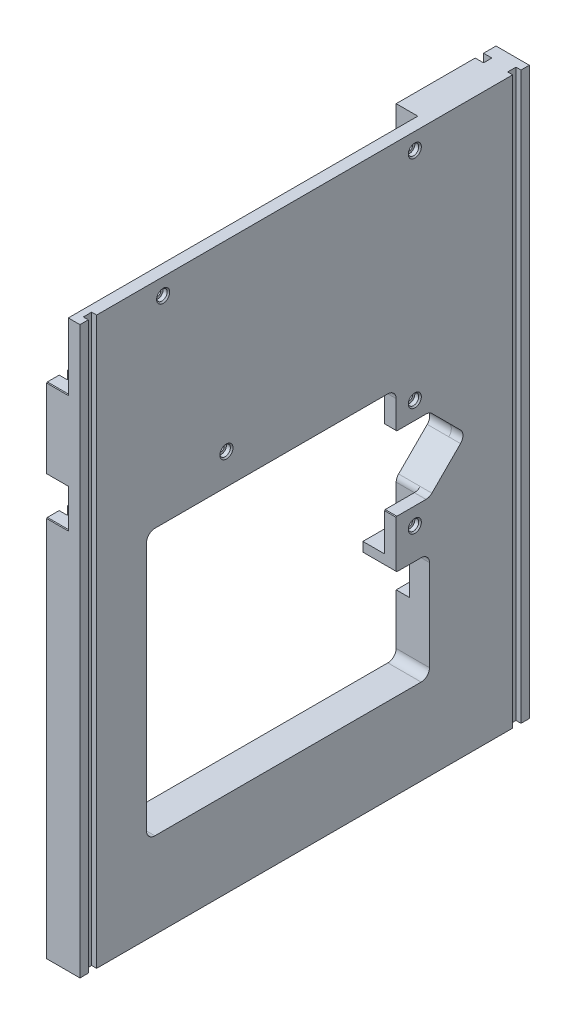
SolidWorks part; units mm, degrees
ref_plane "Front Plane" through (0, 0, 0) normal (0, 0, 1) x (1, 0, 0)
ref_plane "Top Plane" through (0, 0, 0) normal (0, 1, 0) x (1, 0, 0)
ref_plane "Right Plane" through (0, 0, 0) normal (1, 0, 0) x (0, 0, -1)
sketch "Sketch2" plane through (0, 0, 0) normal (1, 0, 0) x (0, 0, -1)
  line L1 (-215.489, 137.2751) -> (127.411, 137.2751)
  line L2 (-215.489, 137.2751) -> (-215.489, -294.5249)
  line L3 (-215.489, -294.5249) -> (127.411, -294.5249)
  line L4 (127.411, 137.2751) -> (127.411, -294.5249)
  dimension "D1" = 342.9
  dimension "D2" = 431.8
extrude "Base" add sketch "Sketch2" along normal blind 25.4
sketch "Sketch3" plane through (0, 0, 0) normal (1, 0, 0) x (0, 0, -1)
  line L0 (-44.039, -294.5249) -> (-44.039, 137.2751) construction
  line L1 (-215.489, -294.5249) -> (127.411, -294.5249) construction
  line L2 (-164.689, -25.9199) -> (-164.689, -229.1199)
  line L3 (-164.689, -229.1199) -> (51.211, -229.1199)
  line L4 (51.211, -146.9509) -> (51.211, -229.1199)
  line L5 (127.411, 137.2751) -> (-215.489, 137.2751) construction
  line L7 (-215.489, 137.2751) -> (-215.489, -294.5249) construction
  line L9 (51.211, -146.9509) -> (25.811, -146.9509)
  line L13 (-164.689, -25.9199) -> (25.811, -25.9199)
  line L14 (25.811, -146.9509) -> (25.811, -25.9199)
  dimension "D1" = 25.4
  dimension "D2" = 163.195
  dimension "D3" = 50.8
  dimension "D4" = 121.031
  dimension "D5" = 190.5
  dimension "D6" = 203.2
extrude "Cut-Extrude3" cut sketch "Sketch3" along normal up to next
sketch "Sketch4" plane through (0, 0, 0) normal (1, 0, 0) x (0, 0, -1)
  line L0 (-215.489, 137.2751) -> (-215.489, -294.5249) construction
  line L1 (19.461, -18.2999) -> (-158.339, -18.2999)
  line L2 (51.211, -15.1249) -> (51.211, 137.2751)
  line L3 (51.211, 137.2751) -> (-202.789, 137.2751)
  line L4 (-164.689, -12.5837) -> (-164.689, -3.0599)
  line L5 (51.211, -146.9509) -> (25.811, -146.9509) construction
  line L6 (25.811, -25.9199) -> (-164.689, -25.9199) construction
  line L7 (-164.689, 25.5151) -> (-215.489, 25.5151)
  line L8 (51.211, -15.1249) -> (51.211, -53.8599)
  line L9 (44.861, -139.3309) -> (25.811, -139.3309)
  line L10 (25.811, -25.9199) -> (25.811, -139.3309)
  line L11 (25.811, -25.9199) -> (-164.689, -25.9199) construction
  line L12 (25.811, -25.9199) -> (19.461, -25.9199)
  line L13 (19.461, -18.2999) -> (19.461, -25.9199)
  line L14 (51.211, -136.1559) -> (51.211, -146.9509)
  line L15 (51.211, -146.9509) -> (44.861, -146.9509)
  line L16 (44.861, -139.3309) -> (44.861, -146.9509)
  line L17 (-44.039, 137.2751) -> (-44.039, -294.5249) construction
  line L18 (-164.689, -12.5837) -> (-164.689, -25.9199)
  line L19 (-164.689, -25.9199) -> (-158.339, -25.9199)
  line L20 (-158.339, -18.2999) -> (-158.339, -25.9199)
  line L22 (-215.489, -294.5249) -> (127.411, -294.5249) construction
  line L23 (51.211, -110.2479) -> (79.405, -82.0539)
  line L24 (-164.689, -3.0599) -> (-215.489, -3.0599)
  line L25 (-215.489, 25.5151) -> (-215.489, -3.0599)
  line L26 (-164.689, 25.5151) -> (-164.689, 86.4751)
  line L27 (-202.789, 137.2751) -> (-215.489, 137.2751)
  line L28 (79.405, -82.0539) -> (51.211, -53.8599)
  line L29 (-164.689, 86.4751) -> (-215.489, 86.4751)
  line L30 (-215.489, 137.2751) -> (-215.489, 90.2851)
  line L31 (-215.489, 90.2851) -> (-215.489, 86.4751)
  line L32 (51.211, -110.2479) -> (51.211, -136.1559)
  dimension "D2" = 7.62
  dimension "D3" = 15.24
  dimension "D4" = 276.606
  dimension "D5" = 25.4
  dimension "D6" = 6.35
  dimension "D7" = 6.35
  dimension "D8" = 7.62
  dimension "D9" = 6.35
  dimension "D10" = 50.8
  dimension "D11" = 111.76
  dimension "D12" = 215.9
  dimension "D13" = 266.7
  dimension "D15" = 45
  dimension "D16" = 29.083
  dimension "D17" = 56.388
extrude "NC pocket" cut sketch "Sketch4" along normal blind 16.51
fillet "Fillet9" radius 6.35 2 edges at (8.255, -110.2479, -51.211) (8.255, -53.8599, -51.211)
fillet "Fillet6" radius 6.35 1 edges at (8.255, -82.0539, -79.405)
hole_wizard "CBORE for M4 SHCS1" positions "Sketch8" profile "Sketch10" counterbore size "M4" standard "ANSI Metric" end condition up to next
sketch "Sketch8" plane through (25.4, 0, 0) normal (1, 0, 0) x (0, 0, -1)
  line L1 (127.411, 137.2751) -> (-215.489, 137.2751) construction
  line L4 (-164.689, -3.0599) -> (-164.689, -229.1199) construction
  line L5 (51.211, -229.1199) -> (51.211, -112.8782) construction
  line L6 (-158.339, -18.2999) -> (19.461, -18.2999) construction
  point P0 (-151.989, 124.5751)
  point P5 (40.035, 124.5751)
  point P7 (40.035, -123.4559)
  point P9 (40.035, -40.5249)
  point P11 (-103.729, -2.4249)
  dimension "D2" = 12.7
  dimension "D3" = 12.7
  dimension "D4" = 11.176
  dimension "D5" = 60.96
  dimension "D6" = 15.875
  dimension "D7" = 11.176
  dimension "D8" = 165.1
  dimension "D9" = 11.176
  dimension "D10" = 82.931
  dimension "D11" = 12.7
sketch "Sketch10" plane through (25.4, 124.5751, 151.989) normal (0, 1, 0) x (0, 0, -1)
  line L0 (0, 0) -> (0, 8.89)
  line L1 (0, 8.89) -> (2.15, 8.89)
  line L3 (2.15, 8.89) -> (2.15, 4)
  line L4 (4, 4) -> (2.15, 4)
  line L5 (4, 4) -> (4, 1)
  line L6 (4, 1) -> (5, 0)
  line L7 (5, 0) -> (0, 0)
  line L8 (-4, 1) -> (-5, 0) construction
  line L11 (0, -6.35) -> (0, 107.95) construction
  dimension "Thru Hole Dia." = 4.3
  dimension "Thru Hole Depth" = 8.89
  dimension "C'Bore Dia." = 8
  dimension "C'Bore Depth" = 4
  dimension "Near C'Sink Dia." = 10
  dimension "Near C'Sink Angle" = 90
sketch "Sketch18" plane through (16.51, 0, 0) normal (-1, 0, 0) x (0, 0, 1)
  circle A0 centre (-40.035, 124.5751) radius 7.1755
  circle A1 centre (151.989, 124.5751) radius 7.1755
  circle A2 centre (103.729, -2.4249) radius 7.1755
  circle A3 centre (-40.035, -40.5249) radius 7.1755
  circle A4 centre (-40.035, -123.4559) radius 7.1755
  dimension "D1" = 14.351
  dimension "D2" = 14.351
  dimension "D3" = 14.351
  dimension "D4" = 14.351
  dimension "D5" = 14.351
extrude "Cut-Extrude4" cut sketch "Sketch18" against normal blind 1.016
hole_wizard "3/8-16 Tapped Hole1" positions "3DSketch1" profile "Sketch14" tap size "3/8-16" standard "ANSI Inch"
sketch3d "3DSketch1"
  line L0 (0, -294.5249, 215.489) -> (0, -294.5249, -127.411) construction
  line L1 (25.4, -294.5249, 215.489) -> (0, -294.5249, 215.489) construction
  point P0 (12.7, -294.5249, -70.261)
  point P2 (12.7, -294.5249, 44.039)
  point P4 (12.7, -294.5249, 158.339)
  dimension "D1" = 12.7
  dimension "D2" = 12.7
  dimension "D3" = 12.7
  dimension "D4" = 114.3
  dimension "D6" = 114.3
  dimension "D5" = 171.45
sketch "Sketch14" plane through (12.7, -294.5249, -70.261) normal (1, 0, 0) x (0, 0, -1)
  line L0 (0, 0) -> (0, 30.3247)
  line L1 (0, 30.3247) -> (3.9687, 27.94)
  line L2 (3.9687, 27.94) -> (3.9687, 0)
  line L5 (3.9687, 0) -> (0, 0)
  line L10 (0, 30.3247) -> (-3.9688, 27.94) construction
  line L11 (0, -6.35) -> (0, 107.95) construction
  dimension "Tap Drill Dia." = 7.9375
  dimension "Tap Drill Depth" = 27.94
  dimension "Drill Angle" = 118
cosmetic thread "Hole Thread1" parameters "D1"=25.4, "D2"=9.525
cosmetic thread "Hole Thread2" parameters "D1"=25.4, "D2"=9.525
cosmetic thread "Hole Thread3" parameters "D1"=25.4, "D2"=9.525
hole_wizard "3/8-16 Tapped Hole2" positions "Sketch15" profile "Sketch17" tap size "3/8-16" standard "ANSI Inch"
sketch "Sketch15" plane through (0, 0, 0) normal (-1, 0, 0) x (0, 0, 1)
  line L0 (215.489, -3.0599) -> (215.489, -294.5249) construction
  line L1 (-127.411, -294.5249) -> (-127.411, 137.2751) construction
  line L2 (215.489, -294.5249) -> (-127.411, -294.5249) construction
  point P0 (186.914, -220.8649)
  point P2 (186.914, -162.4449)
  point P4 (-98.836, -220.8649)
  point P6 (-98.836, -162.4449)
  dimension "D1" = 28.575
  dimension "D2" = 28.575
  dimension "D3" = 28.575
  dimension "D4" = 28.575
  dimension "D5" = 73.66
  dimension "D6" = 58.42
  dimension "D7" = 58.42
  dimension "D8" = 73.66
cosmetic thread "Hole Thread4" parameters "D1"=17.78, "D2"=9.525
cosmetic thread "Hole Thread5" parameters "D1"=17.78, "D2"=9.525
cosmetic thread "Hole Thread6" parameters "D1"=17.78, "D2"=9.525
cosmetic thread "Hole Thread7" parameters "D1"=17.78, "D2"=9.525
sketch "Sketch17" plane through (0, -220.8649, 186.914) normal (0, 1, 0) x (0, 0, 1)
  line L0 (0, 0) -> (0, 22.7047)
  line L1 (0, 22.7047) -> (3.9687, 20.32)
  line L2 (3.9687, 20.32) -> (3.9687, 0)
  line L5 (3.9687, 0) -> (0, 0)
  line L10 (0, 22.7047) -> (-3.9688, 20.32) construction
  line L11 (0, -6.35) -> (0, 107.95) construction
  dimension "Tap Drill Dia." = 7.9375
  dimension "Tap Drill Depth" = 20.32
  dimension "Drill Angle" = 118
sketch "Sketch20" plane through (16.51, 0, 0) normal (-1, 0, 0) x (0, 0, 1)
  line L0 (-51.211, -53.8599) -> (-25.811, -53.8599)
  line L2 (-51.211, -53.8599) -> (-79.405, -82.0539)
  line L3 (-79.405, -82.0539) -> (-51.211, -110.2479)
  line L4 (-25.811, -25.9199) -> (-25.811, -139.3309) construction
  line L6 (-25.811, -53.8599) -> (-25.811, -110.2479)
  line L7 (-25.811, -110.2479) -> (-51.211, -110.2479)
  line L8 (-51.211, -45.3946) -> (-51.211, -54.9122) construction
  line L9 (-51.211, -51.2297) -> (-51.211, 137.2751) construction
  line L10 (-51.211, -116.8371) -> (-51.211, -107.9924) construction
  line L11 (-51.211, -146.9509) -> (-51.211, -112.8782) construction
  line L12 (-74.9149, -77.5638) -> (-53.0709, -55.7198) construction
  line L13 (-53.0709, -108.388) -> (-74.9149, -86.544) construction
extrude "Cut-Extrude5" cut sketch "Sketch20" against normal up to next
fillet "Fillet1" radius 6.35 5 edges at (20.955, -25.9199, 164.689) (12.7, -229.1199, 164.689) (12.7, -229.1199, -51.211) (20.955, -146.9509, -51.211) (20.955, -25.9199, -25.811)
fillet "Fillet2" radius 6.35 3 edges at (20.955, -82.0539, -79.405) (20.955, -110.2479, -51.211) (20.955, -53.8599, -51.211)
chamfer "Chamfer1" distance 0.508 angle 45 9 edges at (8.255, -3.0599, 215.489) (8.255, -3.0599, 164.689) (8.255, 25.5151, 215.489) (8.255, 25.5151, 164.689) (8.255, 86.4751, 215.489) (8.255, 86.4751, 164.689) (12.7, -146.9509, -25.811) (20.955, -110.2479, -25.811) (20.955, -53.8599, -25.811)
sketch "Sketch21" plane through (0, 0, 0) normal (-1, 0, 0) x (0, 0, 1)
  line L0 (215.489, -294.5249) -> (-127.411, -294.5249) construction
  line L1 (205.964, -294.5249) -> (199.614, -294.5249)
  line L2 (205.964, -294.5249) -> (205.964, 137.2751)
  line L3 (205.964, 137.2751) -> (199.614, 137.2751)
  line L4 (199.614, -294.5249) -> (199.614, 137.2751)
  line L5 (-127.411, 137.2751) -> (-51.211, 137.2751) construction
  line L6 (215.489, -3.5679) -> (215.489, -294.5249) construction
  line L7 (-127.411, -294.5249) -> (-127.411, 137.2751) construction
  line L8 (-111.536, -294.5249) -> (-117.886, -294.5249)
  line L9 (-111.536, -294.5249) -> (-111.536, 137.2751)
  line L10 (-111.536, 137.2751) -> (-117.886, 137.2751)
  line L11 (-117.886, -294.5249) -> (-117.886, 137.2751)
  dimension "D1" = 6.35
  dimension "D2" = 9.525
  dimension "D3" = 6.35
  dimension "D4" = 9.525
extrude "Cut-Extrude6" cut sketch "Sketch21" against normal blind 6.35
sketch "Sketch22" plane through (25.4, 0, 0) normal (1, 0, 0) x (0, 0, -1)
  line L0 (-215.489, -294.5249) -> (127.411, -294.5249) construction
  line L1 (-202.789, -294.5249) -> (-209.139, -294.5249)
  line L2 (-202.789, -294.5249) -> (-202.789, 137.2751)
  line L3 (-202.789, 137.2751) -> (-209.139, 137.2751)
  line L4 (-209.139, -294.5249) -> (-209.139, 137.2751)
  line L5 (127.411, 137.2751) -> (-215.489, 137.2751) construction
  line L6 (-215.489, 137.2751) -> (-215.489, -294.5249) construction
  line L7 (127.411, -294.5249) -> (127.411, 137.2751) construction
  line L8 (114.711, 137.2751) -> (121.061, 137.2751)
  line L9 (114.711, 137.2751) -> (114.711, -294.5249)
  line L10 (114.711, -294.5249) -> (121.061, -294.5249)
  line L11 (121.061, 137.2751) -> (121.061, -294.5249)
  dimension "D1" = 6.35
  dimension "D2" = 6.35
  dimension "D3" = 6.35
  dimension "D4" = 6.35
extrude "Cut-Extrude7" cut sketch "Sketch22" against normal blind 3.81
sketch "Sketch23" plane through (0, 0, 0) normal (-1, 0, 0) x (0, 0, 1)
  line L0 (-51.211, -222.7699) -> (-51.211, -112.8782) construction
  line L1 (-51.211, -135.7749) -> (-84.231, -135.7749)
  line L2 (-51.211, -135.7749) -> (-51.211, -184.0349)
  line L3 (-51.211, -184.0349) -> (-84.231, -184.0349)
  line L4 (-84.231, -135.7749) -> (-84.231, -184.0349)
  line L5 (-111.536, 137.2751) -> (-51.211, 137.2751) construction
  dimension "D1" = 33.02
  dimension "D2" = 48.26
  dimension "D3" = 273.05
extrude "Cut-Extrude8" cut sketch "Sketch23" against normal blind 10.16
fillet "Fillet10" radius 6.35 2 edges at (5.08, -135.7749, -84.231) (5.08, -184.0349, -84.231)
